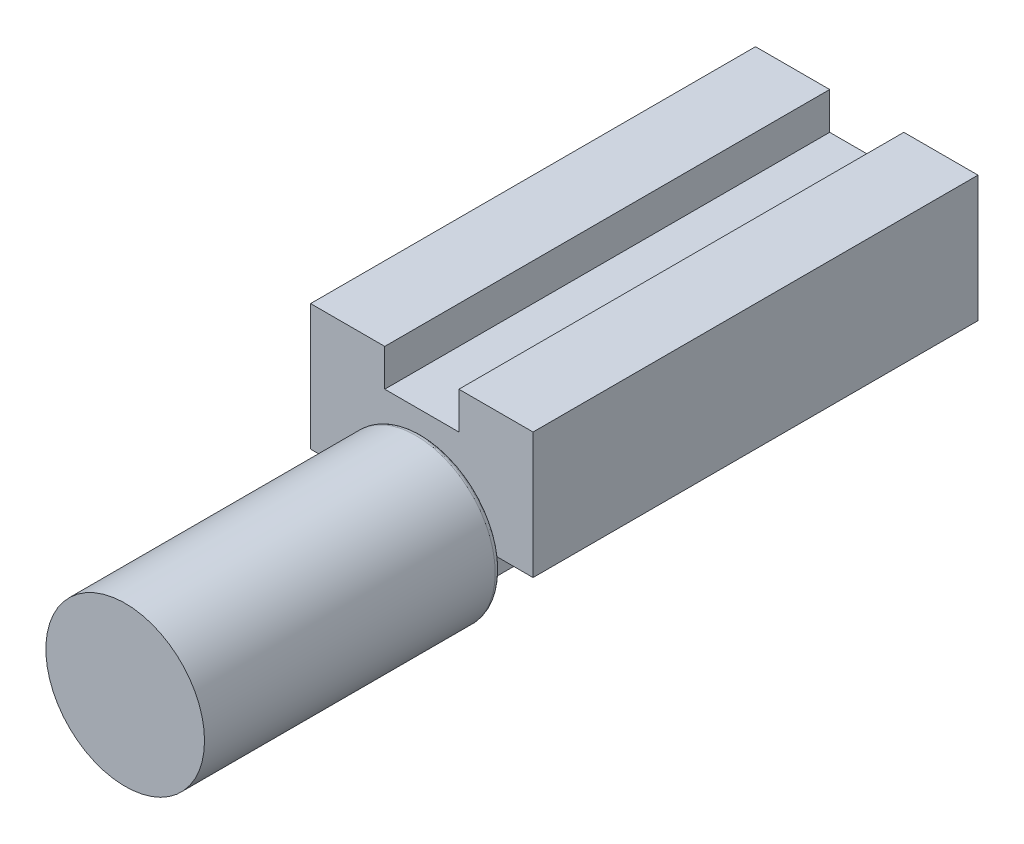
SolidWorks part; units mm, degrees
material "6061-T6 (SS)"
ref_plane "Front Plane" through (0, 0, 0) normal (0, 0, 1) x (1, 0, 0)
ref_plane "Top Plane" through (0, 0, 0) normal (0, 1, 0) x (1, 0, 0)
ref_plane "Right Plane" through (0, 0, 0) normal (1, 0, 0) x (0, 0, -1)
sketch "Sketch1" plane through (0, 0, 0) normal (0, 0, 1) x (1, 0, 0)
  line L0 (-38.8493, -0.5105) -> (-38.8493, 1.6262)
  line L1 (-47.3964, -5.6388) -> (-34.5758, -5.6388)
  line L2 (-47.3964, -5.6388) -> (-47.3964, -0.5105)
  line L3 (-43.1229, -0.5105) -> (-38.8493, -0.5105)
  line L6 (-47.3964, -0.5105) -> (-47.3964, 1.6262)
  line L7 (-47.3964, 1.6262) -> (-43.1229, 1.6262)
  line L8 (-43.1229, -0.5105) -> (-43.1229, 1.6262)
  line L13 (-38.8493, 1.6262) -> (-34.5758, 1.6262)
  line L14 (-34.5758, 1.6262) -> (-34.5758, -5.6388)
  dimension "D1" = 5.1283
  dimension "D2" = 2.1368
  dimension "D3" = 2.1368
  dimension "D4" = 4.2736
  dimension "D5" = 4.2736
  dimension "D6" = 7.265
  dimension "D7" = 12.8207
extrude "Boss-Extrude1" add sketch "Sketch1" along normal blind 25.6413
sketch "Sketch2" plane through (0, 0, 25.6413) normal (0, 0, 1) x (1, 0, 0)
  line L1 (-47.3964, -5.6388) -> (-34.5758, -5.6388) construction
  line L3 (-36.7125, -5.6388) -> (-45.2596, -5.6388)
  line L4 (-36.7125, -5.6388) -> (-36.7125, -6.6645)
  line L5 (-36.7125, -6.6645) -> (-45.2596, -6.6645)
  line L6 (-45.2596, -5.6388) -> (-45.2596, -6.6645)
  dimension "D1" = 8.5471
  dimension "D2" = 1.0257
extrude "Boss-Extrude2" add sketch "Sketch2" against normal blind 12.8207 separate body
sketch "Sketch3" plane through (0, 0, 25.6413) normal (0, 0, 1) x (1, 0, 0)
  circle A0 centre (-40.9861, -6.1516) radius 4.572
  point P0 (-40.9861, -6.1516)
  dimension "D1" = 9.144
extrude "Boss-Extrude3" add sketch "Sketch3" along normal blind 17.0942
fillet "Fillet11" radius 0.3419 1 edges at (-36.4141, -6.1516, 25.6413)
equation "\"da\"= 2 * ( ( 4 * 0.12 ) / ( pi ) ) ^ ( 1 / 3 )"
equation "\"fillet\"= 0.04in"
equation "\"te\"= 0.245"
equation "\"La\"= 2in"
equation "\"Wb\"= 1in"
equation "\"Lb\"= 1.5in"
equation "\"tb\"= 0.12in"
equation "\"Lc\"= 3in"
equation "\"bc\"= 1.5in"
equation "\"hc\"= 0.6in"
equation "\"td\"= 0.04"
equation "\"Le\"= 0.5in"
equation "\"be\"= 1.5in"
equation "\"wd\"= 1.5in"
equation "\"0.04inin\"=0.12"
